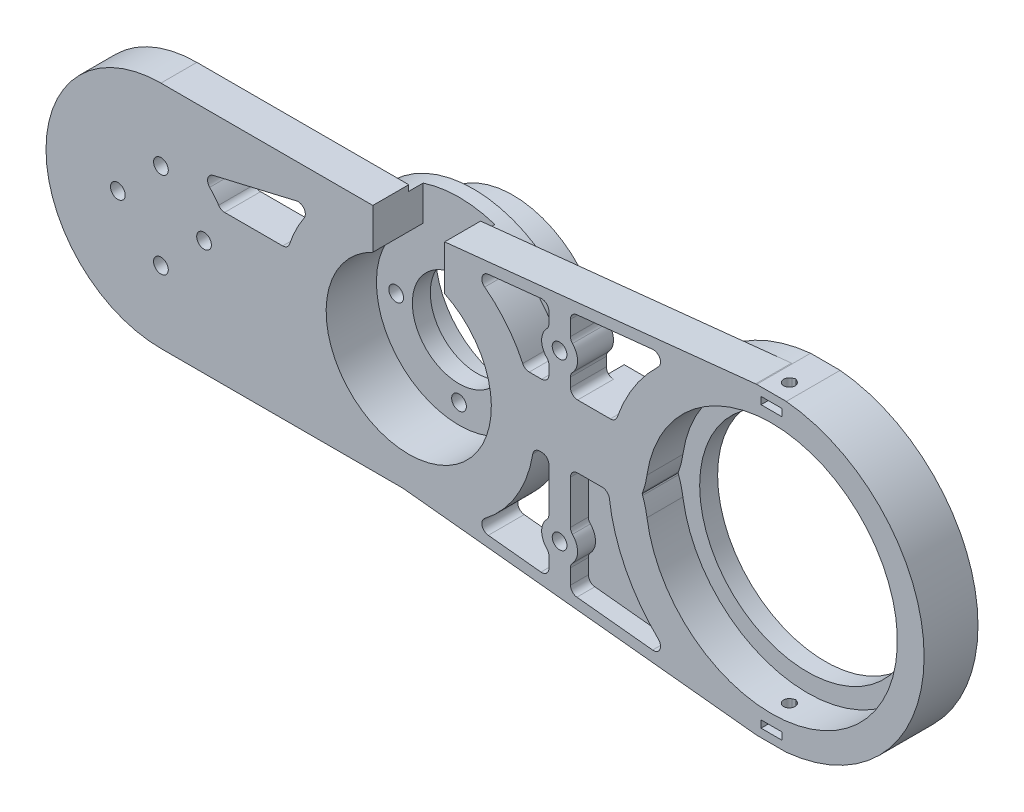
SolidWorks part; units mm, degrees
ref_plane "Front Plane" through (0, 0, 0) normal (1, 0, 0) x (0, 1, 0)
ref_plane "Top Plane" through (0, 0, 0) normal (0, 0, 1) x (0, 1, 0)
ref_plane "Right Plane" through (0, 0, 0) normal (0, 1, 0) x (-1, 0, 0)
sketch "Reference" plane through (0, 0, 0) normal (0, 0, 1) x (0, 1, 0)
  line L0 (0, 0) -> (0, -98) construction
  line L1 (-36.4734, -93.5) -> (-24.5638, 3.0306)
  line L2 (36.4734, -93.5) -> (24.5638, 3.0306)
  circle A0 centre (0, 0) radius 24.75
  circle A1 centre (0, -98) radius 36.75
  dimension "D1" = 49.5
  dimension "D3" = 73.5
  dimension "D2" = 98
sketch "Motor" plane through (0, 0, 0) normal (0, 0, 1) x (0, 1, 0)
  circle A0 centre (0, 0) radius 13
  circle A1 centre (0, 0) radius 23
  circle A2 centre (0, 0) radius 21.5
  circle A3 centre (0, 0) radius 25
  circle A4 centre (0, 0) radius 32
  circle A5 centre (0, 0) radius 17.5 construction
  circle A6 centre (0, 17.5) radius 2.05
  circle A7 centre (0, 17.5) radius 4.25
  circle A8 centre (17.5, 0) radius 4.25
  circle A9 centre (17.5, 0) radius 2.05
  circle A10 centre (0, -17.5) radius 4.25
  circle A11 centre (0, -17.5) radius 2.05
  circle A12 centre (-17.5, 0) radius 4.25
  circle A13 centre (-17.5, 0) radius 2.05
  point P23 (0, 0)
  dimension "D1" = 64
  dimension "D2" = 26
  dimension "D3" = 43
  dimension "D4" = 46
  dimension "D5" = 50
  dimension "D6" = 4
extrude "Motor1" add sketch "Motor" against normal blind 5 from offset 19 contours A1 A12 A2 A7 A8 A10 | A3 A1 | A12 A2 A10 A8 A7 A0 | A2 A10 A11 | A2 A8 A9 | A2 A7 A6 | A2 A12 A13 | A2 A12 | A2 A7 | A2 A8 | A2 A10 region at (0, -22.3495, 0) region at (0.7915, 21.3669, 0) region at (0, 21.5885, 0) region at (0, 13.1894, 0) region at (-19.8109, 3.4248, 0) region at (-21.5885, 0, 0) region at (21.5885, 0, 0) region at (21.3815, 0, 0) region at (-4.0558, -16.7124, 0) region at (0, -21.5885, 0) region at (0, -24.2929, 0) offset against normal yes
extrude "Motor2" add sketch "Motor<4>" against normal blind 10 from surface contours A3 A1 | A1 A12 A2 A7 A8 A10 region at (0, -22.3495, 0) region at (0, -24.2929, 0) starting at face at (25, 0, -24)
sketch "Motor<4>" plane through (0, 0, 0) normal (0, 0, 1) x (0, 1, 0) same geometry as "Motor"
extrude "Motor3" add sketch "Motor<5>" along normal blind 18 from offset 23 contours A4 A3 | A3 A1 region at (0, -24.2929, 0) region at (0, -31.0949, 0) offset against normal yes
sketch "Motor<5>" plane through (0, 0, 0) normal (0, 0, 1) x (0, 1, 0) same geometry as "Motor"
sketch "Main" plane through (0, 0, -5) normal (0, 0, 1) x (1, 0, 0)
  line L0 (0, 0) -> (101, 0) construction
  line L1 (0, 0) -> (-69, 0) construction
  line L2 (-69, 32) -> (-1.6679, 32)
  line L3 (-69, -32) -> (-1.6679, -32)
  line L4 (-3.3267, -31.8266) -> (96.5817, -42.2697)
  line L5 (-3.3267, 31.8266) -> (96.5817, 42.2697)
  line L6 (65.95, 0) -> (65, 0) construction
  line L7 (65, 0) -> (66.0797, 3.0124)
  line L8 (65, 0) -> (66.0797, -3.0124)
  circle A0 centre (101, 0) radius 30
  circle A1 centre (101, 0) radius 35.05
  circle A2 centre (101, 0) radius 42.5
  circle A3 centre (-69, 0) radius 16.25
  circle A4 centre (-69, 0) radius 32
  circle A5 centre (-69, 0) radius 12 construction
  circle A10 centre (0, 0) radius 32 construction
  circle A11 centre (-69, -12) radius 2.05
  circle A12 centre (-81, 0) radius 2.05
  circle A13 centre (-69, 12) radius 2.05
  circle A14 centre (-57, 0) radius 2.05
  point P21 (-65, -4)
  point P31 (-69, 0)
  circle M1 centre (0, 0) radius 32
  dimension "D2" = 85
  dimension "D3" = 70.1
  dimension "D4" = 60
  dimension "D6" = 64
  dimension "D7" = 32.5
  dimension "D8" = 4
  dimension "D1" = 101
  dimension "D5" = 69
extrude "Main1" add sketch "Main" against normal blind 10 contours A4 A3 | A4 L3 L4 L5 L2 M1 | A2 L5 L4 M1 | A2 A1 L8 L7 region at (-34.5026, 0, -5) region at (-47.0126, 21.9874, -5) region at (45.7476, 0, -5) region at (128.6425, 30.6824, -5)
extrude "Main2" add sketch "Main<3>" against normal blind 7.5 contours A3 A14 A13 A12 A11 region at (-69, 0, -5)
sketch "Main<3>" plane through (0, 0, -5) normal (0, 0, 1) x (1, 0, 0) same geometry as "Main"
extrude "Main3" add sketch "Main<4>" against normal blind 5 from surface contours A1 A0 | A2 A1 L8 L7 | A1 L7 L8 region at (128.6425, 30.6824, -5) region at (65.661, 0, -5) region at (102.4649, 34.0271, -5) starting at face at (11.1243, 0, -15)
sketch "Main<4>" plane through (0, 0, -5) normal (0, 0, 1) x (1, 0, 0) same geometry as "Main"
sketch "LimitSwitch" plane through (0, 0, -15) normal (0, 0, -1) x (1, 0, 0)
  line L0 (56, 0) -> (56, -7.5) construction
  line L1 (45, 0) -> (45, -11.6)
  line L2 (45, 0) -> (45, 28.6)
  line L3 (45, 28.6) -> (45, 30.6)
  line L4 (45, -11.6) -> (45, -13.6)
  line L5 (45, 30.6) -> (71.5061, 30.6)
  line L6 (45, 28.6) -> (69.5629, 28.6)
  line L7 (45, -11.6) -> (60.1137, -11.6)
  line L8 (45, -13.6) -> (60.7348, -13.6)
  line L9 (45, 0) -> (56, 0) construction
  line L10 (101, 0) -> (56, 0) construction
  line L11 (56, 0) -> (56, 24.5) construction
  line L12 (45, 30.6) -> (45, 36.878)
  line L13 (-1.6679, 32) -> (96.5817, 42.2697) construction
  line L14 (96.5817, 42.2697) -> (45, 36.878)
  circle A0 centre (101, 0) radius 42.5 construction
  arc A1 (96.5817, 42.2697) -> (96.5817, -42.2697) centre (101, 0) ccw construction
  circle A2 centre (56, -7.5) radius 2.05
  circle A3 centre (56, 24.5) radius 2.05
  arc A4 (96.5817, 42.2697) -> (60.7348, -13.6) centre (101, 0) ccw
  arc M5 (96.5817, -42.2697) -> (96.5817, 42.2697) centre (101, 0) cw
  dimension "D1" = 11.6
  dimension "D2" = 28.6
extrude "LimitSwitch1" add sketch "LimitSwitch" along normal blind 5 contours L3 L6 L5 M5 | L1 L7 L6 L2 A3 A2 M5 | L4 L8 L7 M5 region at (53.235, -10.4283, -15) region at (52.7087, 12.6067, -15) region at (57.7628, -29.6127, -15)
extrude "LimitSwitch2" cut sketch "Sketch6<6>" against normal blind 2 contours A3 | A2
sketch "Sketch6<6>" plane through (0, 0, -15) normal (0, 0, -1) x (1, 0, 0) same geometry as "LimitSwitch"
fillet "Fillet1" radius 25 2 edges at (66.0797, -3.0124, -10) (66.0797, 3.0124, -10)
sketch "Tensioning" plane through (0, 0, -5) normal (0, 0, 1) x (1, 0, 0)
  line L0 (0, 0) -> (42, 0) construction
  line L1 (42, 23) -> (42, -23) construction
  circle A0 centre (42, 23) radius 1.6
  circle A1 centre (42, 23) radius 2.05
  circle A2 centre (42, -23) radius 1.6
  circle A3 centre (42, -23) radius 2.05
  point P6 (42, 0)
  dimension "D1" = 42
extrude "Tenstioning1" cut sketch "Tensioning" against normal blind 10 contours A0 | A2 region at (42, 23, -5)
extrude "Tensioning2" cut sketch "Tensioning<4>" against normal blind 7
sketch "Tensioning<4>" plane through (0, 0, -5) normal (0, 0, 1) x (1, 0, 0) same geometry as "Tensioning"
sketch "ScrewAccess" plane through (0, 0, -5) normal (0, 0, 1) x (1, 0, 0)
  line L0 (0, 0) -> (0, 20) construction
  line L1 (0, 20) -> (-10, 20) construction
  line L3 (-10, 20) -> (10, 20)
  line L4 (-10, 20) -> (-10, 35)
  line L5 (-10, 35) -> (10, 35)
  line L6 (10, 20) -> (10, 35)
extrude "SrewAccess1" cut sketch "ScrewAccess" against normal blind 14 contours L4 L3 L6 L5
sketch "BearingPlier" plane through (0, 0, -5) normal (0, 0, 1) x (1, 0, 0)
  line L0 (0, 0) -> (101, 0) construction
  line L1 (101, 39) -> (101, -39) construction
  line L2 (101, 39) -> (101, 42.3) construction
  line L3 (98.1, 40) -> (103.9, 40)
  line L4 (98.1, 40) -> (98.1, 38)
  line L5 (98.1, 38) -> (103.9, 38)
  line L6 (103.9, 40) -> (103.9, 38)
  line L7 (98.1, 40) -> (103.9, 38) construction
  line L8 (98.1, 38) -> (103.9, 40) construction
  line L9 (98.1, -40) -> (103.9, -40)
  line L10 (98.1, -40) -> (98.1, -38)
  line L11 (98.1, -38) -> (103.9, -38)
  line L12 (103.9, -40) -> (103.9, -38)
  line L13 (98.1, -40) -> (103.9, -38) construction
  line L14 (98.1, -38) -> (103.9, -40) construction
  line L15 (101, -39) -> (101, -42.3) construction
  line L16 (105.1183, -42.3) -> (96.8817, -42.3)
  line L17 (105.1183, 42.3) -> (96.8817, 42.3)
  arc A0 (96.8817, -42.3) -> (105.1183, -42.3) centre (101, 0) ccw
  arc A1 (105.1183, 42.3) -> (96.8817, 42.3) centre (101, 0) ccw
  point P5 (101, 0)
  point P19 (101, -42.3)
  point P22 (101, -42.3)
  point P25 (101, 42.3)
  arc M20 (96.5817, -42.2697) -> (96.5817, 42.2697) centre (101, 0) ccw
extrude "BearingPlier1" cut sketch "BearingPlier" against normal blind 15 contours L17 M20 | L16 M20 region at (101, -42.38, -5) region at (101, 42.38, -5)
extrude "BearingPlier2" cut sketch "Sketch9<3>" against normal blind 7.9 contours L9 L12 L11 L10 | L6 L3 L4 L5 region at (101, 39, -5) region at (101, -39, -5)
sketch "Sketch9<3>" plane through (0, 0, -5) normal (0, 0, 1) x (1, 0, 0) same geometry as "BearingPlier"
sketch "BearingPlierHole" plane through (0, -42.3, 0) normal (0, -1, 0) x (1, 0, 0)
  line L0 (101, -5) -> (101, -9.9871) construction
  line L1 (105.1183, -5) -> (96.8817, -5) construction
  line L2 (101, -9.9871) -> (101, -11.7871) construction
  line L3 (100.267, -11.4094) -> (101, -11.7871)
  line L4 (101.733, -11.4094) -> (101, -11.7871)
  arc A0 (101.733, -11.4094) -> (100.267, -11.4094) centre (101, -9.9871) ccw
extrude "BearingPlierHole1" cut sketch "BearingPlierHole" against normal blind 84.9
sketch "Sketch12" plane through (0, 0, -5) normal (0, 0, 1) x (1, 0, 0)
  line L0 (-72.7092, 15.821) -> (-7.3043, 31.1552)
  line L1 (56.1348, 13.6) -> (47.0209, 13.6)
  line L2 (-3.3267, 31.8266) -> (36.9487, 36.0365)
  line L3 (-72.7092, -15.821) -> (-7.3043, -31.1552)
  line L5 (-1.6679, -32) -> (96.5817, -42.2697) construction
  line L6 (-54.4726, 17.0152) -> (-31.2499, 22.4598)
  line L7 (-54.4726, -17.0152) -> (-31.2499, -22.4598)
  line L8 (22.1463, -31.4729) -> (36.813, -33.0059)
  line L9 (22.1463, 31.4729) -> (36.813, 33.0059)
  line L10 (-36.5103, -4) -> (-48.6146, -4)
  line L13 (53.8805, -4) -> (47.0209, -4)
  line L15 (-35.105, 9.6894) -> (-51.254, 9.6894)
  line L16 (45, 13.6) -> (60.7348, 13.6) construction
  line L17 (-3.3267, 31.8266) -> (96.5817, 42.2697) construction
  line L19 (45.0209, 32.062) -> (45.0209, 27.8776)
  line L21 (39.0209, 31.0168) -> (39.0209, 27.9202)
  line L22 (45.0209, 18.1224) -> (45.0209, 15.6)
  line L23 (39.0209, 18.0798) -> (39.0209, 15.6)
  line L24 (37.0209, 13.6) -> (33.5506, 13.6)
  line L25 (45.0209, -6) -> (45.0209, -18.1224)
  line L26 (39.0209, -6) -> (39.0209, -18.0798)
  line L27 (45.0209, -27.8776) -> (45.0209, -32.062)
  line L28 (39.0209, -27.9202) -> (39.0209, -31.0168)
  line L29 (46.813, -34.0512) -> (67.8968, -36.255)
  line L30 (16.4749, -30.8801) -> (74.4328, -36.9382) construction
  line L31 (37.0209, -4) -> (36.5103, -4)
  line L32 (45.0209, -36.8802) -> (96.5817, -42.2697)
  line L33 (-3.3267, -31.8266) -> (96.5817, -42.2697) construction
  line L34 (46.813, 34.0512) -> (67.8968, 36.255)
  line L35 (16.4749, 30.8801) -> (74.4328, 36.9382) construction
  line L36 (-58.4289, 16.0877) -> (-25.6982, 23.7614) construction
  line L37 (-58.4289, -16.0877) -> (-25.6982, -23.7614) construction
  arc A0 (96.5817, 42.2697) -> (96.5817, -42.2697) centre (101, 0) ccw
  arc A1 (-72.7092, -15.821) -> (-72.7092, 15.821) centre (-69, 0) ccw
  arc A2 (-7.3043, 31.1552) -> (-7.3043, -31.1552) centre (0, 0) ccw
  arc A3 (-3.3267, -31.8266) -> (-3.3267, 31.8266) centre (0, 0) ccw
  arc A4 (-55.4264, -13.6499) -> (-50.5333, -5.4353) centre (-69, 0) ccw
  arc A5 (-29.1289, 19.4038) -> (-33.2074, 11.0575) centre (0, 0) ccw
  arc A6 (69.4898, 32.8231) -> (58.0238, 14.9432) centre (101, 0) ccw
  arc A7 (21.1459, -27.89) -> (34.5367, -5.6757) centre (0, 0) ccw
  arc A8 (-34.5367, -5.6757) -> (-29.1289, -19.4038) centre (0, 0) ccw
  arc A9 (-25.6982, 23.7614) -> (-25.6982, -23.7614) centre (0, 0) ccw construction
  arc A10 (-52.9242, 10.5892) -> (-55.4264, 13.6499) centre (-69, 0) ccw
  arc A11 (-58.4289, -16.0877) -> (-58.4289, 16.0877) centre (-69, 0) ccw construction
  arc A12 (55.8645, -5.7474) -> (69.4898, -32.8231) centre (101, 0) ccw
  arc A13 (74.4328, 36.9382) -> (74.4328, -36.9382) centre (101, 0) ccw construction
  arc A14 (31.737, 14.7568) -> (21.1459, 27.89) centre (0, 0) ccw
  arc A15 (16.4749, -30.8801) -> (16.4749, 30.8801) centre (0, 0) ccw construction
  arc A16 (45.5864, 19.516) -> (45.5864, 26.484) centre (42, 23) ccw
  arc A17 (38.4435, -19.4856) -> (38.4435, -26.5144) centre (42, -23) ccw
  arc A18 (38.4435, 26.5144) -> (38.4435, 19.4856) centre (42, 23) ccw
  arc A19 (45.5864, -26.484) -> (45.5864, -19.516) centre (42, -23) ccw
  arc A20 (-51.254, 9.6894) -> (-52.9242, 10.5892) centre (-51.254, 11.6894) cw
  arc A21 (-55.4264, 13.6499) -> (-54.4726, 17.0152) centre (-54.0161, 15.068) cw
  arc A22 (-31.2499, 22.4598) -> (-29.1289, 19.4038) centre (-30.7934, 20.5126) cw
  arc A23 (-35.105, 9.6894) -> (-33.2074, 11.0575) centre (-35.105, 11.6894) ccw
  arc A24 (-29.1289, -19.4038) -> (-31.2499, -22.4598) centre (-30.7934, -20.5126) cw
  arc A25 (-36.5103, -4) -> (-34.5367, -5.6757) centre (-36.5103, -6) cw
  arc A26 (-48.6146, -4) -> (-50.5333, -5.4353) centre (-48.6146, -6) ccw
  arc A27 (-55.4264, -13.6499) -> (-54.4726, -17.0152) centre (-54.0161, -15.068) ccw
  arc A28 (39.0209, -6) -> (37.0209, -4) centre (37.0209, -6) ccw
  arc A29 (36.5103, -4) -> (34.5367, -5.6757) centre (36.5103, -6) ccw
  arc A30 (22.1463, -31.4729) -> (21.1459, -27.89) centre (22.3542, -29.4837) cw
  arc A31 (36.813, -33.0059) -> (39.0209, -31.0168) centre (37.0209, -31.0168) ccw
  arc A32 (39.0209, -27.9202) -> (38.4435, -26.5144) centre (37.0209, -27.9202) ccw
  arc A33 (38.4435, -19.4856) -> (39.0209, -18.0798) centre (37.0209, -18.0798) ccw
  arc A34 (45.5864, -19.516) -> (45.0209, -18.1224) centre (47.0209, -18.1224) cw
  arc A35 (45.0209, -27.8776) -> (45.5864, -26.484) centre (47.0209, -27.8776) cw
  arc A36 (46.813, -34.0512) -> (45.0209, -32.062) centre (47.0209, -32.062) cw
  arc A37 (69.4898, -32.8231) -> (67.8968, -36.255) centre (68.1047, -34.2659) cw
  arc A38 (53.8805, -4) -> (55.8645, -5.7474) centre (53.8805, -6) cw
  arc A39 (45.0209, -6) -> (47.0209, -4) centre (47.0209, -6) cw
  arc A40 (21.1459, 27.89) -> (22.1463, 31.4729) centre (22.3542, 29.4837) cw
  arc A41 (33.5506, 13.6) -> (31.737, 14.7568) centre (33.5506, 15.6) cw
  arc A42 (37.0209, 13.6) -> (39.0209, 15.6) centre (37.0209, 15.6) ccw
  arc A43 (39.0209, 18.0798) -> (38.4435, 19.4856) centre (37.0209, 18.0798) ccw
  arc A44 (39.0209, 27.9202) -> (38.4435, 26.5144) centre (37.0209, 27.9202) cw
  arc A45 (39.0209, 31.0168) -> (36.813, 33.0059) centre (37.0209, 31.0168) ccw
  arc A46 (45.0209, 32.062) -> (46.813, 34.0512) centre (47.0209, 32.062) cw
  arc A47 (45.0209, 27.8776) -> (45.5864, 26.484) centre (47.0209, 27.8776) ccw
  arc A48 (45.0209, 18.1224) -> (45.5864, 19.516) centre (47.0209, 18.1224) cw
  arc A49 (47.0209, 13.6) -> (45.0209, 15.6) centre (47.0209, 15.6) cw
  arc A50 (56.1348, 13.6) -> (58.0238, 14.9432) centre (56.1348, 15.6) ccw
  arc A51 (69.4898, 32.8231) -> (67.8968, 36.255) centre (68.1047, 34.2659) ccw
  point P44 (42.0209, 0)
  point P63 (-52.3663, 9.6894)
  point P77 (-34.7707, -4)
  point P85 (39.0209, -4)
  point P101 (45.0209, -26.9842)
  point P109 (55.6762, -4)
  point P123 (39.0209, 27.0156)
  point P128 (45.0209, 33.8639)
  dimension "D3" = 2
  dimension "D1" = 3
  dimension "D2" = 3
extrude "Cut-Extrude8" cut sketch "Sketch12" against normal blind 10 contours L15 A20 A10 A21 L6 A22 A5 A23 | L26 A33 A17 A32 L28 A31 L8 A30 A7 A29 L31 A28 | A18 A43 L23 A42 L24 A41 A14 A40 L9 A45 L21 A44 | A16 A47 L19 A46 L34 A51 A6 A50 L1 A49 L22 A48
extrude "Cut-Extrude10" cut sketch "Sketch12<5>" against normal blind 5 contours A12 A37 L29 A36 L27 A35 A19 A34 L25 A39 L13 A38
sketch "Sketch12<5>" plane through (0, 0, -5) normal (0, 0, 1) x (1, 0, 0) same geometry as "Sketch12"
